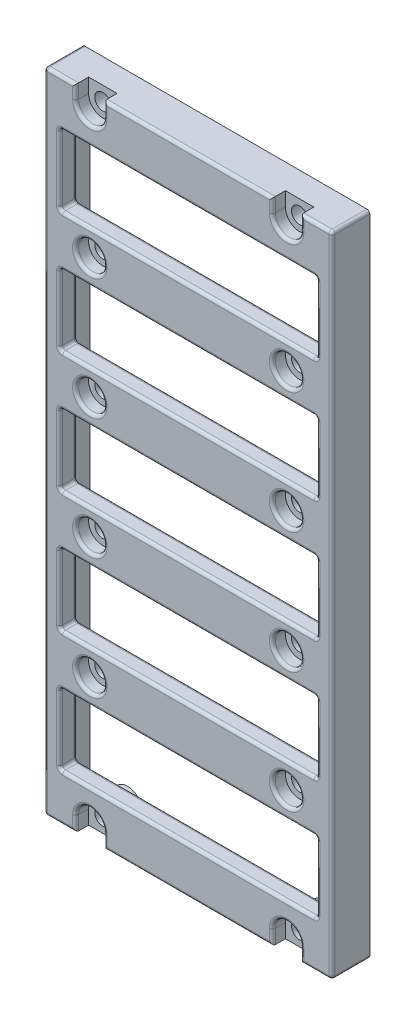
SolidWorks part; units mm, degrees
material "Nylon 101"
ref_plane "Front Plane" through (0, 0, 0) normal (0, 0, 1) x (1, 0, 0)
ref_plane "Top Plane" through (0, 0, 0) normal (0, 1, 0) x (1, 0, 0)
ref_plane "Right Plane" through (0, 0, 0) normal (1, 0, 0) x (0, 0, -1)
sketch "Sketch1" plane through (0, 0, 0) normal (0, 0, 1) x (1, 0, 0)
  line L1 (-39.37, -124.9522) -> (-63.5, -124.9522) construction
  line L2 (-15.24, -177.7842) -> (-15.24, -72.1202)
  line L4 (-63.5, -177.7842) -> (-63.5, -72.1202)
  line L5 (-15.24, -177.7842) -> (-63.5, -72.1202) construction
  line L6 (-15.24, -72.1202) -> (-63.5, -177.7842) construction
  line L8 (-15.24, -72.1202) -> (-15.24, -70.5962)
  line L9 (-15.24, -70.5962) -> (-63.5, -70.5962)
  line L10 (-15.24, -177.7842) -> (-15.24, -179.3082)
  line L11 (-15.24, -179.3082) -> (-63.5, -179.3082)
  line L12 (-63.5, -177.7842) -> (-63.5, -179.3082)
  line L13 (-15.24, -177.7842) -> (-63.5, -179.3082) construction
  line L14 (-15.24, -179.3082) -> (-63.5, -177.7842) construction
  line L15 (-63.5, -72.1202) -> (-63.5, -70.5962)
  point P4 (-39.37, -124.9522)
  point P8 (-39.37, -178.5462)
  dimension "D1" = 1.524
extrude "Boss-Extrude1" add sketch "Sketch1" along normal blind 6.35
hole_wizard "CBORE for #2 Socket Head Cap Screw1" positions "Sketch3" profile "Sketch2" counterbore size "#2" standard "ANSI Inch" end condition through all
sketch "Sketch3" plane through (0, 0, 6.35) normal (0, 0, 1) x (1, 0, 0)
  line L0 (-22.86, -179.3082) -> (-22.86, -70.5962) construction
  line L1 (-63.5, -179.3082) -> (-15.24, -179.3082) construction
  line L2 (-15.24, -70.5962) -> (-63.5, -70.5962) construction
  line L3 (-20.828, -74.1522) -> (-24.892, -74.1522) construction
  line L4 (-39.37, -179.3082) -> (-39.37, -70.5962) construction
  line L7 (-57.912, -74.1522) -> (-53.848, -74.1522) construction
  line L8 (-55.88, -179.3082) -> (-55.88, -70.5962) construction
  point P24 (-22.86, -74.1522)
  point P25 (-22.86, -72.9838)
  point P28 (-22.86, -94.4722)
  point P31 (-22.86, -114.7922)
  point P34 (-22.86, -135.1122)
  point P37 (-22.86, -155.4322)
  point P40 (-22.86, -176.9206)
  point P53 (-55.88, -176.9206)
  point P54 (-55.88, -155.4322)
  point P55 (-55.88, -135.1122)
  point P56 (-55.88, -114.7922)
  point P57 (-55.88, -94.4722)
  point P58 (-55.88, -72.9838)
  dimension "D1" = 2.3876
  dimension "D2" = 2.3876
sketch "Sketch2" plane through (-22.86, -72.9838, 6.35) normal (1, 0, 0) x (0, -1, 0)
  line L0 (0, 0) -> (0, 6.35)
  line L1 (0, 6.35) -> (1.3525, 6.35)
  line L3 (1.3525, 6.35) -> (1.3526, 2.1844)
  line L4 (1.3526, 2.1844) -> (2.3812, 2.1844)
  line L5 (2.3812, 2.1844) -> (2.3812, 0)
  line L7 (2.3812, 0) -> (0, 0)
  line L11 (0, -6.35) -> (0, 107.95) construction
  dimension "Thru Hole Dia." = 2.7051
  dimension "Thru Hole Depth" = 6.35
  dimension "C'Bore Dia." = 4.7625
  dimension "C'Bore Depth" = 2.1844
sketch "Sketch4" plane through (0, 0, 6.35) normal (0, 0, 1) x (1, 0, 0)
  line L0 (-63.5, -179.3082) -> (-15.24, -179.3082) construction
  line L1 (-20.4788, -176.9206) -> (-25.2412, -176.9206)
  line L2 (-20.4788, -176.9206) -> (-20.4788, -179.3082)
  line L3 (-20.4788, -179.3082) -> (-25.2412, -179.3082)
  line L4 (-25.2412, -176.9206) -> (-25.2412, -179.3082)
  line L5 (-20.4788, -176.9206) -> (-25.2412, -179.3082) construction
  line L6 (-20.4788, -179.3082) -> (-25.2412, -176.9206) construction
  line L7 (-22.86, -176.9206) -> (-22.86, -179.3082) construction
  line L8 (-39.37, -179.3082) -> (-39.37, -124.9522) construction
  line L9 (-39.37, -124.9522) -> (-63.5, -124.9522) construction
  line L10 (-63.5, -70.5962) -> (-63.5, -179.3082) construction
  line L11 (-58.2613, -176.9206) -> (-53.4988, -176.9206)
  line L12 (-58.2613, -176.9206) -> (-58.2613, -179.3082)
  line L13 (-58.2613, -179.3082) -> (-53.4988, -179.3082)
  line L14 (-53.4988, -176.9206) -> (-53.4988, -179.3082)
  line L15 (-20.4788, -72.9838) -> (-25.2413, -72.9838)
  line L16 (-20.4788, -72.9838) -> (-20.4788, -70.5962)
  line L17 (-20.4788, -70.5962) -> (-25.2413, -70.5962)
  line L18 (-25.2413, -72.9838) -> (-25.2413, -70.5962)
  line L19 (-53.4988, -72.9838) -> (-53.4988, -70.5962)
  line L20 (-58.2612, -70.5962) -> (-53.4988, -70.5962)
  line L21 (-58.2612, -72.9838) -> (-58.2612, -70.5962)
  line L22 (-58.2612, -72.9838) -> (-53.4988, -72.9838)
  circle A0 centre (-22.86, -176.9206) radius 2.3812 construction
  point P4 (-22.86, -178.1144)
extrude "Cut-Extrude1" cut sketch "Sketch4" against normal up to surface (2.1844 mm away) up to face at (-21.5074, -176.9206, 4.1656)
sketch "Sketch5" plane through (0, 0, 6.35) normal (0, 0, 1) x (1, 0, 0)
  line L0 (-17.78, -151.2254) -> (-60.96, -139.3191) construction
  line L1 (-17.78, -171.5454) -> (-60.96, -171.5454)
  line L2 (-17.78, -171.5454) -> (-17.78, -159.6391)
  line L3 (-17.78, -159.6391) -> (-60.96, -159.6391)
  line L4 (-60.96, -171.5454) -> (-60.96, -159.6391)
  line L5 (-17.78, -171.5454) -> (-60.96, -159.6391) construction
  line L6 (-17.78, -159.6391) -> (-60.96, -171.5454) construction
  line L7 (-17.78, -139.3191) -> (-60.96, -151.2254) construction
  line L8 (-17.78, -151.2254) -> (-17.78, -139.3191)
  line L9 (-17.78, -151.2254) -> (-60.96, -151.2254)
  line L10 (-60.96, -151.2254) -> (-60.96, -139.3191)
  line L11 (-17.78, -139.3191) -> (-60.96, -139.3191)
  line L12 (-17.78, -130.9054) -> (-60.96, -118.9991) construction
  line L13 (-17.78, -118.9991) -> (-60.96, -130.9054) construction
  line L14 (-17.78, -130.9054) -> (-17.78, -118.9991)
  line L15 (-17.78, -130.9054) -> (-60.96, -130.9054)
  line L16 (-60.96, -130.9054) -> (-60.96, -118.9991)
  line L17 (-17.78, -118.9991) -> (-60.96, -118.9991)
  line L18 (-17.78, -110.5854) -> (-60.96, -98.6791) construction
  line L19 (-17.78, -98.6791) -> (-60.96, -110.5854) construction
  line L20 (-17.78, -110.5854) -> (-17.78, -98.6791)
  line L21 (-17.78, -110.5854) -> (-60.96, -110.5854)
  line L22 (-60.96, -110.5854) -> (-60.96, -98.6791)
  line L23 (-17.78, -98.6791) -> (-60.96, -98.6791)
  line L24 (-17.78, -90.2654) -> (-60.96, -78.3591) construction
  line L25 (-17.78, -78.3591) -> (-60.96, -90.2654) construction
  line L26 (-17.78, -90.2654) -> (-17.78, -78.3591)
  line L27 (-17.78, -90.2654) -> (-60.96, -90.2654)
  line L28 (-60.96, -90.2654) -> (-60.96, -78.3591)
  line L29 (-17.78, -78.3591) -> (-60.96, -78.3591)
  point P4 (-39.37, -165.5922)
  point P13 (-39.37, -145.2722)
  point P18 (-39.37, -124.9522)
  point P23 (-39.37, -104.6322)
  point P28 (-39.37, -84.3122)
  dimension "D1" = 5
extrude "Cut-Extrude2" cut sketch "Sketch5" against normal through all
sketch "Sketch6" plane through (0, 0, 0) normal (0, 0, -1) x (-1, 0, 0)
  line L0 (20.4788, -72.9838) -> (20.4788, -70.5962) construction
  line L1 (25.2413, -70.5962) -> (25.2413, -72.9838) construction
  line L2 (53.4988, -72.9838) -> (53.4988, -70.5962) construction
  line L3 (58.2612, -70.5962) -> (58.2612, -72.9838) construction
  line L4 (20.4788, -179.3082) -> (20.4788, -176.9206) construction
  line L5 (25.2412, -176.9206) -> (25.2412, -179.3082) construction
  line L6 (53.4988, -179.3082) -> (53.4988, -176.9206) construction
  line L7 (58.2612, -176.9206) -> (58.2613, -179.3082) construction
  line L8 (20.4788, -72.9838) -> (20.4788, -71.8662)
  line L9 (25.2413, -71.8662) -> (25.2413, -72.9838)
  line L10 (53.4988, -72.9838) -> (53.4988, -71.8662)
  line L11 (58.2612, -71.8662) -> (58.2612, -72.9838)
  line L12 (20.4788, -178.0382) -> (20.4788, -176.9206)
  line L13 (25.2412, -176.9206) -> (25.2412, -178.0382)
  line L14 (53.4988, -178.0382) -> (53.4988, -176.9206)
  line L15 (58.2612, -176.9206) -> (58.2612, -178.0382)
  line L17 (62.23, -71.8662) -> (58.2612, -71.8662)
  line L18 (16.51, -71.8662) -> (16.51, -178.0382)
  line L19 (16.51, -178.0382) -> (20.4788, -178.0382)
  line L20 (15.24, -70.5962) -> (15.24, -179.3082)
  line L21 (15.24, -179.3082) -> (63.5, -179.3082)
  line L22 (63.5, -179.3082) -> (63.5, -70.5962)
  line L23 (63.5, -70.5962) -> (15.24, -70.5962)
  line L24 (15.24, -70.5962) -> (15.24, -179.3082) construction
  line L25 (15.24, -179.3082) -> (63.5, -179.3082) construction
  line L26 (63.5, -179.3082) -> (63.5, -70.5962) construction
  line L27 (63.5, -70.5962) -> (15.24, -70.5962) construction
  line L28 (62.23, -178.0382) -> (62.23, -71.8662)
  line L29 (17.78, -110.5854) -> (60.96, -110.5854)
  line L30 (17.78, -98.6791) -> (17.78, -110.5854)
  line L31 (60.96, -98.6791) -> (17.78, -98.6791)
  line L32 (60.96, -110.5854) -> (60.96, -98.6791)
  line L33 (17.78, -110.5854) -> (60.96, -110.5854)
  line L34 (17.78, -98.6791) -> (17.78, -110.5854)
  line L35 (60.96, -98.6791) -> (17.78, -98.6791)
  line L36 (60.96, -110.5854) -> (60.96, -98.6791)
  line L37 (17.78, -90.2654) -> (60.96, -90.2654)
  line L38 (17.78, -78.3591) -> (17.78, -90.2654)
  line L39 (60.96, -78.3591) -> (17.78, -78.3591)
  line L40 (60.96, -90.2654) -> (60.96, -78.3591)
  line L41 (17.78, -90.2654) -> (60.96, -90.2654)
  line L42 (17.78, -78.3591) -> (17.78, -90.2654)
  line L43 (60.96, -78.3591) -> (17.78, -78.3591)
  line L44 (60.96, -90.2654) -> (60.96, -78.3591)
  line L45 (17.78, -130.9054) -> (60.96, -130.9054)
  line L46 (17.78, -118.9991) -> (17.78, -130.9054)
  line L47 (60.96, -118.9991) -> (17.78, -118.9991)
  line L48 (60.96, -130.9054) -> (60.96, -118.9991)
  line L49 (17.78, -130.9054) -> (60.96, -130.9054)
  line L50 (17.78, -118.9991) -> (17.78, -130.9054)
  line L51 (60.96, -118.9991) -> (17.78, -118.9991)
  line L52 (60.96, -130.9054) -> (60.96, -118.9991)
  line L53 (17.78, -151.2254) -> (60.96, -151.2254)
  line L54 (17.78, -139.3191) -> (17.78, -151.2254)
  line L55 (60.96, -139.3191) -> (17.78, -139.3191)
  line L56 (60.96, -151.2254) -> (60.96, -139.3191)
  line L57 (17.78, -151.2254) -> (60.96, -151.2254)
  line L58 (17.78, -139.3191) -> (17.78, -151.2254)
  line L59 (60.96, -139.3191) -> (17.78, -139.3191)
  line L60 (60.96, -151.2254) -> (60.96, -139.3191)
  line L61 (17.78, -159.6391) -> (17.78, -171.5454)
  line L62 (60.96, -159.6391) -> (17.78, -159.6391)
  line L63 (60.96, -171.5454) -> (60.96, -159.6391)
  line L64 (17.78, -171.5454) -> (60.96, -171.5454)
  line L65 (17.78, -159.6391) -> (17.78, -171.5454)
  line L66 (60.96, -159.6391) -> (17.78, -159.6391)
  line L67 (60.96, -171.5454) -> (60.96, -159.6391)
  line L68 (17.78, -171.5454) -> (60.96, -171.5454)
  line L69 (20.4788, -71.8662) -> (16.51, -71.8662)
  line L70 (62.23, -71.8662) -> (16.51, -71.8662) construction
  line L71 (53.4988, -71.8662) -> (25.2413, -71.8662)
  line L72 (25.2412, -178.0382) -> (53.4988, -178.0382)
  line L73 (16.51, -178.0382) -> (62.23, -178.0382) construction
  line L74 (58.2612, -178.0382) -> (62.23, -178.0382)
  arc A0 (20.4788, -72.9838) -> (25.2413, -72.9838) centre (22.86, -72.9838) ccw construction
  arc A1 (53.4988, -72.9838) -> (58.2612, -72.9838) centre (55.88, -72.9838) ccw construction
  arc A2 (25.2412, -176.9206) -> (20.4788, -176.9206) centre (22.86, -176.9206) ccw construction
  arc A3 (58.2612, -176.9206) -> (53.4988, -176.9206) centre (55.88, -176.9206) ccw construction
  arc A4 (20.4788, -72.9838) -> (25.2413, -72.9838) centre (22.86, -72.9838) ccw
  arc A5 (53.4988, -72.9838) -> (58.2612, -72.9838) centre (55.88, -72.9838) ccw
  arc A6 (25.2412, -176.9206) -> (20.4788, -176.9206) centre (22.86, -176.9206) ccw
  arc A7 (58.2612, -176.9206) -> (53.4988, -176.9206) centre (55.88, -176.9206) ccw
  circle A8 centre (55.88, -155.4322) radius 2.3812 construction
  circle A9 centre (22.86, -155.4322) radius 2.3812 construction
  circle A10 centre (22.86, -135.1122) radius 2.3812 construction
  circle A11 centre (55.88, -135.1122) radius 2.3812 construction
  circle A12 centre (55.88, -114.7922) radius 2.3812 construction
  circle A13 centre (22.86, -114.7922) radius 2.3812 construction
  circle A14 centre (22.86, -94.4722) radius 2.3812 construction
  circle A15 centre (55.88, -94.4722) radius 2.3812 construction
  circle A16 centre (55.88, -155.4322) radius 2.3812
  circle A17 centre (22.86, -155.4322) radius 2.3812
  circle A18 centre (22.86, -135.1122) radius 2.3812
  circle A19 centre (55.88, -135.1122) radius 2.3812
  circle A20 centre (55.88, -114.7922) radius 2.3812
  circle A21 centre (22.86, -114.7922) radius 2.3812
  circle A22 centre (22.86, -94.4722) radius 2.3812
  circle A23 centre (55.88, -94.4722) radius 2.3812
  dimension "D1" = 0
  dimension "D2" = 0
  dimension "D3" = 0
  dimension "D4" = 0
  dimension "D5" = 0
  dimension "D6" = 0
  dimension "D7" = 1.27
extrude "Cut-Extrude3" cut sketch "Sketch6" against normal offset from surface (3.4036 mm away) 0.762 up to face at (-54.5274, -155.4322, 4.1656)
fillet "Fillet1" radius 0.508 132 edges at (-25.2413, -71.79, 6.35) (-22.86, -75.3651, 6.35) (-20.4788, -71.79, 6.35) (-17.8594, -70.5962, 6.35) (-15.24, -124.9522, 6.35) (-17.8594, -179.3082, 6.35) (-20.4788, -178.1144, 6.35) (-22.86, -174.5394, 6.35) (-25.2412, -178.1144, 6.35) (-39.37, -179.3082, 6.35) (-53.4988, -178.1144, 6.35) (-55.88, -174.5394, 6.35) (-58.2613, -178.1144, 6.35) (-60.8806, -179.3082, 6.35) (-63.5, -124.9522, 6.35) (-60.8806, -70.5962, 6.35) (-58.2612, -71.79, 6.35) (-55.88, -75.3651, 6.35) (-53.4988, -71.79, 6.35) (-39.37, -70.5962, 6.35) (-53.4988, -94.4722, 6.35) (-53.4988, -114.7922, 6.35) (-53.4988, -135.1122, 6.35) (-53.4988, -155.4322, 6.35) (-20.4788, -155.4322, 6.35) (-20.4788, -135.1122, 6.35) (-20.4788, -114.7922, 6.35) (-20.4788, -94.4722, 6.35) (-60.96, -165.5922, 6.35) (-39.37, -171.5454, 6.35) (-17.78, -165.5922, 6.35) (-39.37, -159.6391, 6.35) (-39.37, -139.3191, 6.35) (-60.96, -145.2722, 6.35) (-39.37, -151.2254, 6.35) (-17.78, -145.2722, 6.35) (-39.37, -118.9991, 6.35) (-60.96, -124.9522, 6.35) (-39.37, -130.9054, 6.35) (-17.78, -124.9522, 6.35) (-39.37, -98.6791, 6.35) (-60.96, -104.6322, 6.35) (-39.37, -110.5854, 6.35) (-17.78, -104.6322, 6.35) (-39.37, -78.3591, 6.35) (-60.96, -84.3122, 6.35) (-39.37, -90.2654, 6.35) (-17.78, -84.3122, 6.35) (-58.2612, -155.4322, 3.4036) (-25.2412, -135.1122, 3.4036) (-58.2612, -114.7922, 3.4036) (-25.2412, -94.4722, 3.4036) (-17.78, -104.6322, 3.4036) (-39.37, -110.5854, 3.4036) (-60.96, -104.6322, 3.4036) (-39.37, -98.6791, 3.4036) (-17.78, -84.3122, 3.4036) (-39.37, -90.2654, 3.4036) (-60.96, -84.3122, 3.4036) (-39.37, -78.3591, 3.4036) (-17.78, -124.9522, 3.4036) (-39.37, -130.9054, 3.4036) (-60.96, -124.9522, 3.4036) (-39.37, -118.9991, 3.4036) (-17.78, -145.2722, 3.4036) (-39.37, -151.2254, 3.4036) (-60.96, -145.2722, 3.4036) (-39.37, -139.3191, 3.4036) (-39.37, -159.6391, 3.4036) (-17.78, -165.5922, 3.4036) (-39.37, -171.5454, 3.4036) (-60.96, -165.5922, 3.4036) (-58.2613, -94.4722, 3.4036) (-25.2412, -114.7922, 3.4036) (-58.2612, -135.1122, 3.4036) (-25.2412, -155.4322, 3.4036) (-25.2413, -72.425, 3.4036) (-39.37, -71.8662, 3.4036) (-53.4988, -72.425, 3.4036) (-55.88, -75.3651, 3.4036) (-58.2612, -72.425, 3.4036) (-60.2456, -71.8662, 3.4036) (-62.23, -124.9522, 3.4036) (-60.2456, -178.0382, 3.4036) (-58.2612, -177.4794, 3.4036) (-55.88, -174.5394, 3.4036) (-53.4988, -177.4794, 3.4036) (-39.37, -178.0382, 3.4036) (-25.2412, -177.4794, 3.4036) (-22.86, -174.5394, 3.4036) (-20.4788, -177.4794, 3.4036) (-18.4944, -178.0382, 3.4036) (-16.51, -124.9522, 3.4036) (-18.4944, -71.8662, 3.4036) (-20.4788, -72.425, 3.4036) (-22.86, -75.3651, 3.4036) (-15.24, -70.5962, 3.175) (-63.5, -70.5962, 3.175) (-63.5, -179.3082, 3.175) (-15.24, -179.3082, 3.175) (-20.4788, -71.8662, 1.7018) (-16.51, -178.0382, 1.7018) (-20.4788, -178.0382, 1.7018) (-25.2412, -178.0382, 1.7018) (-53.4988, -178.0382, 1.7018) (-58.2612, -178.0382, 1.7018) (-62.23, -178.0382, 1.7018) (-62.23, -71.8662, 1.7018) (-58.2612, -71.8662, 1.7018) (-53.4988, -71.8662, 1.7018) (-25.2413, -71.8662, 1.7018) (-16.51, -71.8662, 1.7018) (-17.78, -98.6791, 4.8768) (-17.78, -110.5854, 4.8768) (-60.96, -110.5854, 4.8768) (-60.96, -98.6791, 4.8768) (-17.78, -78.3591, 4.8768) (-17.78, -90.2654, 4.8768) (-60.96, -90.2654, 4.8768) (-60.96, -78.3591, 4.8768) (-17.78, -118.9991, 4.8768) (-17.78, -130.9054, 4.8768) (-60.96, -130.9054, 4.8768) (-60.96, -118.9991, 4.8768) (-17.78, -151.2254, 4.8768) (-60.96, -151.2254, 4.8768) (-60.96, -139.3191, 4.8768) (-17.78, -139.3191, 4.8768) (-60.96, -159.6391, 4.8768) (-17.78, -171.5454, 4.8768) (-60.96, -171.5454, 4.8768) (-17.78, -159.6391, 4.8768)
sketch "Sketch7" plane through (0, 0, 0) normal (0, 0, -1) x (-1, 0, 0)
  line L1 (59.5078, -161.9188) -> (19.5816, -161.9188)
  line L2 (59.5078, -161.9188) -> (59.5078, -88.1954)
  line L3 (59.5078, -88.1954) -> (19.5816, -88.1954)
  line L4 (19.5816, -161.9188) -> (19.5816, -88.1954)
  line L5 (59.5078, -161.9188) -> (19.5816, -88.1954) construction
  line L6 (59.5078, -88.1954) -> (19.5816, -161.9188) construction
  point P4 (39.5447, -125.0571)
extrude "Cut-Extrude4" cut sketch "Sketch7" against normal blind 2.54
